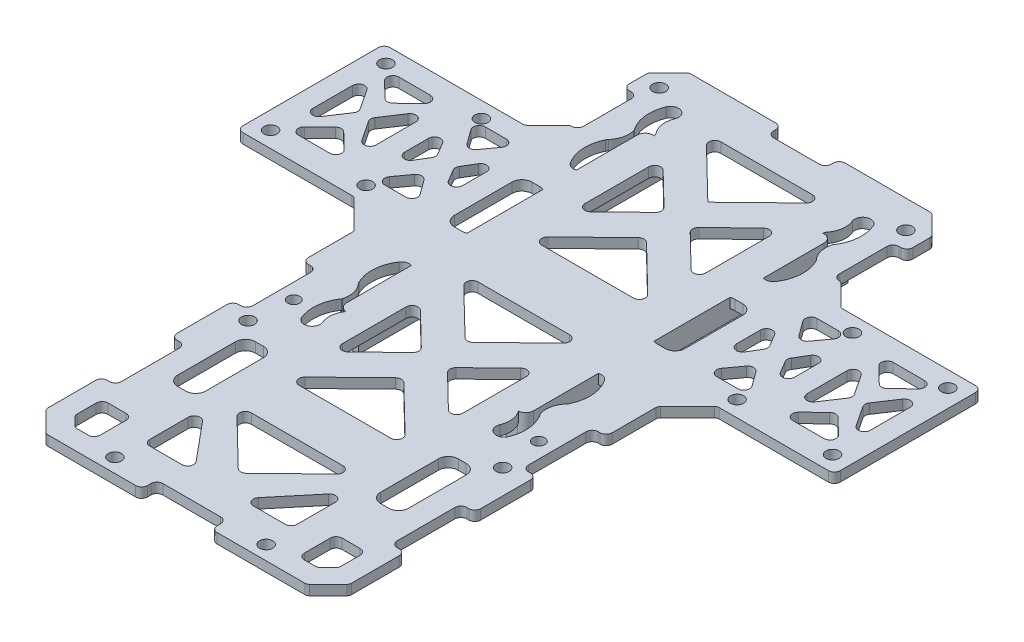
SolidWorks part; units mm, degrees
ref_plane "Ön Düzlem" through (0, 0, 0) normal (0, 0, 1) x (1, 0, 0)
ref_plane "Üst Düzlem" through (0, 0, 0) normal (0, 1, 0) x (1, 0, 0)
ref_plane "Sağ Düzlem" through (0, 0, 0) normal (1, 0, 0) x (0, 0, -1)
sketch "Çizim1" plane through (0, 0, 0) normal (0, 1, 0) x (1, 0, 0)
  line L0 (0, 0) -> (0, 152) construction
  line L1 (-5.75, 152) -> (5.75, 152)
  line L2 (7.25, 153.5) -> (7.25, 154)
  line L3 (8.75, 155.5) -> (30.05, 155.5)
  line L4 (30.8773, 155.1573) -> (35.2967, 150.7379)
  line L5 (35.6394, 149.9106) -> (35.6394, 145.6106)
  line L6 (34.1394, 144.1106) -> (33.6394, 144.1106)
  line L7 (32.1394, 142.6106) -> (32.1394, 130.6106)
  line L8 (34.4172, 128.7884) -> (39.4377, 123.7679)
  line L9 (40.2155, 123.4458) -> (73.5655, 123.4458)
  line L10 (75.0655, 121.9458) -> (75.0655, 87.9458)
  line L11 (73.5655, 86.4458) -> (46.1155, 86.4458)
  line L12 (45.2882, 86.1031) -> (38.5, 79.3148)
  line L13 (38.1573, 78.4875) -> (38.1573, 67.4875)
  line L14 (36.6573, 65.9875) -> (36.1573, 65.9875)
  line L15 (34.6573, 64.4875) -> (34.6573, 49.9875)
  line L16 (36.1573, 48.4875) -> (36.6573, 48.4875)
  line L17 (38.1573, 46.9875) -> (38.1573, 34.4875)
  line L18 (36.6573, 32.9875) -> (36.1573, 32.9875)
  line L19 (34.6573, 31.4875) -> (34.6573, 16.9875)
  line L20 (36.1573, 15.4875) -> (36.6573, 15.4875)
  line L21 (38.1573, 13.9875) -> (38.1573, 1.9875)
  line L22 (37.8351, 1.2097) -> (33.0975, -3.5279)
  line L23 (32.3197, -3.8501) -> (10.25, -3.8501)
  line L24 (8.75, -2.3501) -> (8.75, -1.5)
  line L25 (7.25, 0) -> (-7.25, 0)
  line L26 (-11.5, 144.5) -> (11.5, 144.5)
  line L27 (12.5458, 141.9246) -> (0, 129.7241)
  line L29 (4.3673, 123.0754) -> (12.5937, 131.0754)
  line L30 (15.1394, 130) -> (15.1394, 114)
  line L31 (12.5937, 112.9246) -> (4.3673, 120.9246)
  line L32 (-18.2259, 122) -> (18.2259, 122) construction
  line L33 (-11.5, 99.5) -> (11.5, 99.5)
  line L34 (12.5458, 102.0754) -> (1.0458, 113.2589)
  line L36 (-11.5, 91.5) -> (11.5, 91.5) construction
  line L37 (-11.5, 38.5) -> (11.5, 38.5)
  line L38 (12.5458, 41.0754) -> (1.0458, 52.2589)
  line L40 (15.1394, 53) -> (15.1394, 69)
  line L41 (4.3673, 59.9246) -> (12.5937, 51.9246)
  line L42 (12.5937, 70.0754) -> (4.3673, 62.0754)
  line L44 (12.5458, 80.9246) -> (1.0458, 69.7411)
  line L45 (-11.5, 83.5) -> (11.5, 83.5)
  line L46 (-12.9097, 32.5) -> (12.9097, 32.5) construction
  line L48 (12.5458, 23.9246) -> (1.0458, 12.7411)
  line L49 (-11.5, 26.5) -> (11.5, 26.5)
  line L50 (7.8474, 8.96) -> (15.8474, 18.5647)
  line L51 (18.5, 17.6047) -> (18.5, 8)
  line L52 (17, 6.5) -> (9, 6.5)
  line L53 (27.1573, 10.6499) -> (31.6573, 10.6499)
  line L54 (33.1573, 9.1499) -> (33.1573, 4.4177)
  line L55 (32.7179, 3.357) -> (30.9502, 1.5893)
  line L56 (29.8895, 1.1499) -> (27.1573, 1.1499)
  line L57 (25.6573, 2.6499) -> (25.6573, 9.1499)
  line L58 (22, 67.5) -> (26.5, 67.5) construction
  line L59 (24.5, 112) -> (26.5, 112)
  line L60 (22, 109.5) -> (22, 95)
  line L61 (24.5, 92.5) -> (26.5, 92.5)
  line L62 (29, 109.5) -> (29, 95)
  line L63 (24.5, 42.5) -> (26.5, 42.5)
  line L64 (29, 25.5) -> (29, 40)
  line L65 (24.5, 23) -> (26.5, 23)
  line L66 (22, 25.5) -> (22, 40)
  line L67 (19.1523, 99.4458) -> (36.6573, 99.4458) construction
  line L68 (37.8532, 115.7624) -> (40.5032, 112.1255)
  line L69 (42.9278, 112.1255) -> (45.5778, 115.7624)
  line L70 (44.3655, 118.1458) -> (39.0655, 118.1458)
  line L71 (40.9015, 105.5088) -> (43.9435, 105.5088) construction
  line L72 (42.9278, 98.8921) -> (45.5778, 95.2552)
  line L73 (37.8532, 95.2552) -> (40.5032, 98.8921)
  line L74 (44.3655, 92.8718) -> (39.0655, 92.8718)
  line L75 (44.4115, 104.7362) -> (46.2143, 101.7362)
  line L76 (49, 102.5088) -> (49, 108.5088)
  line L77 (46.2143, 109.2814) -> (44.4115, 106.2814)
  line L78 (41.7155, 112.5406) -> (41.7155, 108.4846) construction
  line L79 (34.431, 102.5088) -> (34.431, 108.5088)
  line L80 (39.0195, 104.7362) -> (37.2167, 101.7362)
  line L81 (37.2167, 109.2814) -> (39.0195, 106.2814)
  line L82 (58.1655, 118.1458) -> (66.0655, 118.1458)
  line L83 (67.1093, 115.5685) -> (63.1593, 111.7413)
  line L84 (61.0717, 111.7413) -> (57.1217, 115.5685)
  line L85 (67.1093, 95.4491) -> (63.1593, 99.2763)
  line L86 (58.1655, 92.8718) -> (66.0655, 92.8718)
  line L87 (61.0717, 99.2763) -> (57.1217, 95.4491)
  line L88 (63.9989, 104.6796) -> (67.3155, 99.6796)
  line L89 (70.0655, 100.5088) -> (70.0655, 110.5088)
  line L90 (67.3155, 111.338) -> (63.9989, 106.338)
  line L91 (62.1155, 113.6588) -> (62.1155, 107.6588) construction
  line L95 (54.1655, 100.5088) -> (54.1655, 110.5088)
  line L96 (60.2321, 104.6796) -> (56.9155, 99.6796)
  line L97 (56.9155, 111.338) -> (60.2321, 106.338)
  line L98 (-25.6573, 2.6499) -> (-25.6573, 9.1499)
  line L99 (-29.8895, 1.1499) -> (-27.1573, 1.1499)
  line L100 (-32.7179, 3.357) -> (-30.9502, 1.5893)
  line L101 (-33.1573, 9.1499) -> (-33.1573, 4.4177)
  line L102 (-27.1573, 10.6499) -> (-31.6573, 10.6499)
  line L103 (-17, 6.5) -> (-9, 6.5)
  line L104 (-18.5, 17.6047) -> (-18.5, 8)
  line L105 (-7.8474, 8.96) -> (-15.8474, 18.5647)
  line L106 (-12.5458, 23.9246) -> (-1.0458, 12.7411)
  line L107 (-8.75, -2.3501) -> (-8.75, -1.5)
  line L108 (-32.3197, -3.8501) -> (-10.25, -3.8501)
  line L109 (-37.8351, 1.2097) -> (-33.0975, -3.5279)
  line L110 (-38.1573, 13.9875) -> (-38.1573, 1.9875)
  line L111 (-62.1155, 113.6588) -> (-62.1155, 107.6588) construction
  line L112 (-41.7155, 112.5406) -> (-41.7155, 108.4846) construction
  line L113 (-40.9015, 105.5088) -> (-43.9435, 105.5088) construction
  line L114 (-19.1523, 99.4458) -> (-36.6573, 99.4458) construction
  line L115 (-22, 67.5) -> (-26.5, 67.5) construction
  line L116 (-56.9155, 111.338) -> (-60.2321, 106.338)
  line L117 (-60.2321, 104.6796) -> (-56.9155, 99.6796)
  line L118 (-54.1655, 100.5088) -> (-54.1655, 110.5088)
  line L119 (-67.3155, 111.338) -> (-63.9989, 106.338)
  line L120 (-70.0655, 100.5088) -> (-70.0655, 110.5088)
  line L121 (-63.9989, 104.6796) -> (-67.3155, 99.6796)
  line L122 (-61.0717, 99.2763) -> (-57.1217, 95.4491)
  line L123 (-58.1655, 92.8718) -> (-66.0655, 92.8718)
  line L124 (-67.1093, 95.4491) -> (-63.1593, 99.2763)
  line L125 (-61.0717, 111.7413) -> (-57.1217, 115.5685)
  line L126 (-67.1093, 115.5685) -> (-63.1593, 111.7413)
  line L127 (-58.1655, 118.1458) -> (-66.0655, 118.1458)
  line L128 (-37.2167, 109.2814) -> (-39.0195, 106.2814)
  line L129 (-39.0195, 104.7362) -> (-37.2167, 101.7362)
  line L130 (-34.431, 102.5088) -> (-34.431, 108.5088)
  line L131 (-46.2143, 109.2814) -> (-44.4115, 106.2814)
  line L132 (-49, 102.5088) -> (-49, 108.5088)
  line L133 (-44.4115, 104.7362) -> (-46.2143, 101.7362)
  line L134 (-44.3655, 92.8718) -> (-39.0655, 92.8718)
  line L135 (-37.8532, 95.2552) -> (-40.5032, 98.8921)
  line L136 (-42.9278, 98.8921) -> (-45.5778, 95.2552)
  line L137 (-44.3655, 118.1458) -> (-39.0655, 118.1458)
  line L138 (-42.9278, 112.1255) -> (-45.5778, 115.7624)
  line L139 (-37.8532, 115.7624) -> (-40.5032, 112.1255)
  line L140 (-22, 25.5) -> (-22, 40)
  line L141 (-24.5, 23) -> (-26.5, 23)
  line L142 (-29, 25.5) -> (-29, 40)
  line L143 (-24.5, 42.5) -> (-26.5, 42.5)
  line L144 (-29, 109.5) -> (-29, 95)
  line L145 (-24.5, 92.5) -> (-26.5, 92.5)
  line L146 (-22, 109.5) -> (-22, 95)
  line L147 (-24.5, 112) -> (-26.5, 112)
  line L148 (-12.5458, 80.9246) -> (-1.0458, 69.7411)
  line L149 (-12.5937, 70.0754) -> (-4.3673, 62.0754)
  line L150 (-4.3673, 59.9246) -> (-12.5937, 51.9246)
  line L151 (-15.1394, 53) -> (-15.1394, 69)
  line L152 (-12.5458, 41.0754) -> (-1.0458, 52.2589)
  line L153 (-12.5458, 102.0754) -> (-1.0458, 113.2589)
  line L154 (-12.5937, 112.9246) -> (-4.3673, 120.9246)
  line L155 (-15.1394, 130) -> (-15.1394, 114)
  line L156 (-4.3673, 123.0754) -> (-12.5937, 131.0754)
  line L157 (-12.5458, 141.9246) -> (0, 129.7241)
  line L158 (-36.1573, 15.4875) -> (-36.6573, 15.4875)
  line L159 (-34.6573, 31.4875) -> (-34.6573, 16.9875)
  line L160 (-36.6573, 32.9875) -> (-36.1573, 32.9875)
  line L161 (-38.1573, 46.9875) -> (-38.1573, 34.4875)
  line L162 (-36.1573, 48.4875) -> (-36.6573, 48.4875)
  line L163 (-34.6573, 64.4875) -> (-34.6573, 49.9875)
  line L164 (-36.6573, 65.9875) -> (-36.1573, 65.9875)
  line L165 (-38.1573, 78.4875) -> (-38.1573, 67.4875)
  line L166 (-45.2882, 86.1031) -> (-38.5, 79.3148)
  line L167 (-73.5655, 86.4458) -> (-46.1155, 86.4458)
  line L168 (-75.0655, 121.9458) -> (-75.0655, 87.9458)
  line L169 (-40.2155, 123.4458) -> (-73.5655, 123.4458)
  line L170 (-34.4172, 128.7884) -> (-39.4377, 123.7679)
  line L171 (-32.1394, 142.6106) -> (-32.1394, 130.6106)
  line L172 (-34.1394, 144.1106) -> (-33.6394, 144.1106)
  line L173 (-35.6394, 149.9106) -> (-35.6394, 145.6106)
  line L174 (-30.8773, 155.1573) -> (-35.2967, 150.7379)
  line L175 (-8.75, 155.5) -> (-30.05, 155.5)
  line L176 (-7.25, 153.5) -> (-7.25, 154)
  arc A0 (5.75, 152) -> (7.25, 153.5) centre (5.75, 153.5) ccw
  arc A1 (7.25, 154) -> (8.75, 155.5) centre (8.75, 154) cw
  arc A2 (30.05, 155.5) -> (30.8773, 155.1573) centre (30.05, 154.33) cw
  arc A3 (35.2967, 150.7379) -> (35.6394, 149.9106) centre (34.4694, 149.9106) cw
  arc A4 (35.6394, 145.6106) -> (34.1394, 144.1106) centre (34.1394, 145.6106) cw
  arc A5 (33.6394, 144.1106) -> (32.1394, 142.6106) centre (33.6394, 142.6106) ccw
  arc A6 (32.1394, 130.6106) -> (33.6394, 129.1106) centre (33.6394, 130.6106) ccw
  arc A7 (34.4172, 128.7884) -> (33.6394, 129.1106) centre (33.6394, 128.0106) ccw
  arc A8 (39.4377, 123.7679) -> (40.2155, 123.4458) centre (40.2155, 124.5458) ccw
  arc A9 (73.5655, 123.4458) -> (75.0655, 121.9458) centre (73.5655, 121.9458) cw
  arc A10 (75.0655, 87.9458) -> (73.5655, 86.4458) centre (73.5655, 87.9458) cw
  arc A11 (46.1155, 86.4458) -> (45.2882, 86.1031) centre (46.1155, 85.2758) ccw
  arc A12 (38.5, 79.3148) -> (38.1573, 78.4875) centre (39.3273, 78.4875) ccw
  arc A13 (36.1573, 65.9875) -> (34.6573, 64.4875) centre (36.1573, 64.4875) ccw
  arc A14 (38.1573, 67.4875) -> (36.6573, 65.9875) centre (36.6573, 67.4875) cw
  arc A15 (36.6573, 48.4875) -> (38.1573, 46.9875) centre (36.6573, 46.9875) cw
  arc A16 (34.6573, 49.9875) -> (36.1573, 48.4875) centre (36.1573, 49.9875) ccw
  arc A17 (36.1573, 32.9875) -> (34.6573, 31.4875) centre (36.1573, 31.4875) ccw
  arc A18 (38.1573, 34.4875) -> (36.6573, 32.9875) centre (36.6573, 34.4875) cw
  arc A19 (36.6573, 15.4875) -> (38.1573, 13.9875) centre (36.6573, 13.9875) cw
  arc A20 (34.6573, 16.9875) -> (36.1573, 15.4875) centre (36.1573, 16.9875) ccw
  arc A21 (38.1573, 1.9875) -> (37.8351, 1.2097) centre (37.0573, 1.9875) cw
  arc A22 (33.0975, -3.5279) -> (32.3197, -3.8501) centre (32.3197, -2.7501) cw
  arc A23 (8.75, -1.5) -> (7.25, 0) centre (7.25, -1.5) ccw
  arc A24 (10.25, -3.8501) -> (8.75, -2.3501) centre (10.25, -2.3501) cw
  arc A25 (11.5, 144.5) -> (12.5458, 141.9246) centre (11.5, 143) cw
  arc A27 (12.5937, 131.0754) -> (15.1394, 130) centre (13.6394, 130) cw
  arc A28 (15.1394, 114) -> (12.5937, 112.9246) centre (13.6394, 114) cw
  arc A29 (4.3673, 123.0754) -> (4.3673, 120.9246) centre (5.4131, 122) ccw
  arc A30 (11.5, 99.5) -> (12.5458, 102.0754) centre (11.5, 101) ccw
  arc A32 (11.5, 38.5) -> (12.5458, 41.0754) centre (11.5, 40) ccw
  arc A34 (12.5937, 51.9246) -> (15.1394, 53) centre (13.6394, 53) ccw
  arc A35 (15.1394, 69) -> (12.5937, 70.0754) centre (13.6394, 69) ccw
  arc A36 (4.3673, 59.9246) -> (4.3673, 62.0754) centre (5.4131, 61) cw
  arc A38 (11.5, 83.5) -> (12.5458, 80.9246) centre (11.5, 82) cw
  arc A40 (11.5, 26.5) -> (12.5458, 23.9246) centre (11.5, 25) cw
  arc A41 (15.8474, 18.5647) -> (18.5, 17.6047) centre (17, 17.6047) cw
  arc A42 (18.5, 8) -> (17, 6.5) centre (17, 8) cw
  arc A43 (7.8474, 8.96) -> (9, 6.5) centre (9, 8) ccw
  arc A44 (31.6573, 10.6499) -> (33.1573, 9.1499) centre (31.6573, 9.1499) cw
  arc A45 (27.1573, 10.6499) -> (25.6573, 9.1499) centre (27.1573, 9.1499) ccw
  arc A46 (33.1573, 4.4177) -> (32.7179, 3.357) centre (31.6573, 4.4177) cw
  arc A47 (30.9502, 1.5893) -> (29.8895, 1.1499) centre (29.8895, 2.6499) cw
  arc A48 (27.1573, 1.1499) -> (25.6573, 2.6499) centre (27.1573, 2.6499) cw
  arc A49 (22, 95) -> (24.5, 92.5) centre (24.5, 95) ccw
  arc A50 (26.5, 92.5) -> (29, 95) centre (26.5, 95) ccw
  arc A51 (26.5, 112) -> (29, 109.5) centre (26.5, 109.5) cw
  arc A52 (24.5, 112) -> (22, 109.5) centre (24.5, 109.5) ccw
  arc A53 (26.5, 42.5) -> (29, 40) centre (26.5, 40) cw
  arc A54 (26.5, 23) -> (29, 25.5) centre (26.5, 25.5) ccw
  arc A55 (22, 40) -> (24.5, 42.5) centre (24.5, 40) cw
  arc A56 (24.5, 23) -> (22, 25.5) centre (24.5, 25.5) cw
  arc A57 (23.1394, 137.067) -> (24.1394, 144.5) centre (17.2022, 141.6495) ccw construction
  arc A62 (24.7227, 135.845) -> (25.9893, 145.2601) centre (17.2022, 141.6495) ccw
  arc A63 (21.5562, 138.289) -> (22.2895, 143.7399) centre (17.2022, 141.6495) ccw
  arc A64 (21.5562, 138.289) -> (24.7227, 135.845) centre (23.1394, 137.067) ccw
  arc A65 (25.9893, 145.2601) -> (22.2895, 143.7399) centre (24.1394, 144.5) ccw
  arc A66 (24.6394, 129.567) -> (23.1394, 137.067) centre (30.2159, 134.5823) cw construction
  arc A71 (21.2524, 137.7296) -> (23.1524, 128.2296) centre (30.2159, 134.5823) ccw
  arc A72 (25.0265, 136.4044) -> (26.1265, 130.9044) centre (30.2159, 134.5823) ccw
  arc A73 (25.0265, 136.4044) -> (21.2524, 137.7296) centre (23.1394, 137.067) ccw
  arc A74 (23.1524, 128.2296) -> (26.1265, 130.9044) centre (24.6394, 129.567) ccw
  arc A75 (24.1394, 122.0837) -> (24.6394, 129.567) centre (17.9087, 126.2583) ccw construction
  arc A76 (25.8009, 120.9704) -> (26.4343, 130.4493) centre (17.9087, 126.2583) ccw
  arc A77 (22.4779, 123.1969) -> (22.8446, 128.6847) centre (17.9087, 126.2583) ccw
  arc A78 (22.4779, 123.1969) -> (25.8009, 120.9704) centre (24.1394, 122.0837) ccw
  arc A79 (26.4343, 130.4493) -> (22.8446, 128.6847) centre (24.6394, 129.567) ccw
  arc A80 (24.6394, 69.3246) -> (23.1394, 61.8246) centre (30.2159, 64.3093) ccw construction
  arc A81 (21.2524, 61.162) -> (23.1524, 70.662) centre (30.2159, 64.3093) cw
  arc A82 (25.0265, 62.4871) -> (26.1265, 67.9871) centre (30.2159, 64.3093) cw
  arc A83 (25.0265, 62.4871) -> (21.2524, 61.162) centre (23.1394, 61.8246) cw
  arc A84 (23.1524, 70.662) -> (26.1265, 67.9871) centre (24.6394, 69.3246) cw
  arc A85 (23.1394, 61.8246) -> (24.1394, 54.3915) centre (17.2022, 57.242) cw construction
  arc A86 (24.7227, 63.0466) -> (25.9893, 53.6314) centre (17.2022, 57.242) cw
  arc A87 (21.5562, 60.6025) -> (22.2895, 55.1516) centre (17.2022, 57.242) cw
  arc A88 (21.5562, 60.6025) -> (24.7227, 63.0466) centre (23.1394, 61.8246) cw
  arc A89 (25.9893, 53.6314) -> (22.2895, 55.1516) centre (24.1394, 54.3915) cw
  arc A90 (24.1394, 76.8079) -> (24.6394, 69.3246) centre (17.9087, 72.6332) cw construction
  arc A91 (25.8009, 77.9211) -> (26.4343, 68.4422) centre (17.9087, 72.6332) cw
  arc A92 (22.4779, 75.6946) -> (22.8446, 70.2069) centre (17.9087, 72.6332) cw
  arc A93 (22.4779, 75.6946) -> (25.8009, 77.9211) centre (24.1394, 76.8079) cw
  arc A94 (26.4343, 68.4422) -> (22.8446, 70.2069) centre (24.6394, 69.3246) cw
  arc A95 (40.5032, 112.1255) -> (42.9278, 112.1255) centre (41.7155, 113.0088) ccw
  arc A96 (45.5778, 115.7624) -> (44.3655, 118.1458) centre (44.3655, 116.6458) ccw
  arc A97 (37.8532, 115.7624) -> (39.0655, 118.1458) centre (39.0655, 116.6458) cw
  arc A98 (40.5032, 98.8921) -> (42.9278, 98.8921) centre (41.7155, 98.0088) cw
  arc A99 (45.5778, 95.2552) -> (44.3655, 92.8718) centre (44.3655, 94.3718) cw
  arc A100 (37.8532, 95.2552) -> (39.0655, 92.8718) centre (39.0655, 94.3718) ccw
  arc A101 (49, 108.5088) -> (46.2143, 109.2814) centre (47.5, 108.5088) ccw
  arc A102 (46.2143, 101.7362) -> (49, 102.5088) centre (47.5, 102.5088) ccw
  arc A103 (44.4115, 104.7362) -> (44.4115, 106.2814) centre (45.6972, 105.5088) cw
  arc A104 (37.2167, 101.7362) -> (34.431, 102.5088) centre (35.931, 102.5088) cw
  arc A105 (34.431, 108.5088) -> (37.2167, 109.2814) centre (35.931, 108.5088) cw
  arc A106 (39.0195, 104.7362) -> (39.0195, 106.2814) centre (37.7338, 105.5088) ccw
  arc A107 (66.0655, 118.1458) -> (67.1093, 115.5685) centre (66.0655, 116.6458) cw
  arc A108 (63.1593, 111.7413) -> (61.0717, 111.7413) centre (62.1155, 112.8186) cw
  arc A109 (58.1655, 118.1458) -> (57.1217, 115.5685) centre (58.1655, 116.6458) ccw
  arc A110 (66.0655, 92.8718) -> (67.1093, 95.4491) centre (66.0655, 94.3718) ccw
  arc A111 (63.1593, 99.2763) -> (61.0717, 99.2763) centre (62.1155, 98.199) ccw
  arc A112 (58.1655, 92.8718) -> (57.1217, 95.4491) centre (58.1655, 94.3718) cw
  arc A113 (67.3155, 99.6796) -> (70.0655, 100.5088) centre (68.5655, 100.5088) ccw
  arc A114 (63.9989, 104.6796) -> (63.9989, 106.338) centre (65.2489, 105.5088) cw
  arc A115 (70.0655, 110.5088) -> (67.3155, 111.338) centre (68.5655, 110.5088) ccw
  arc A119 (56.9155, 99.6796) -> (54.1655, 100.5088) centre (55.6655, 100.5088) cw
  arc A120 (60.2321, 104.6796) -> (60.2321, 106.338) centre (58.9821, 105.5088) ccw
  arc A121 (54.1655, 110.5088) -> (56.9155, 111.338) centre (55.6655, 110.5088) cw
  arc A122 (-27.1573, 1.1499) -> (-25.6573, 2.6499) centre (-27.1573, 2.6499) ccw
  arc A123 (-30.9502, 1.5893) -> (-29.8895, 1.1499) centre (-29.8895, 2.6499) ccw
  arc A124 (-33.1573, 4.4177) -> (-32.7179, 3.357) centre (-31.6573, 4.4177) ccw
  arc A125 (-27.1573, 10.6499) -> (-25.6573, 9.1499) centre (-27.1573, 9.1499) cw
  arc A126 (-31.6573, 10.6499) -> (-33.1573, 9.1499) centre (-31.6573, 9.1499) ccw
  arc A127 (-7.8474, 8.96) -> (-9, 6.5) centre (-9, 8) cw
  arc A128 (-18.5, 8) -> (-17, 6.5) centre (-17, 8) ccw
  arc A129 (-15.8474, 18.5647) -> (-18.5, 17.6047) centre (-17, 17.6047) ccw
  arc A130 (-10.25, -3.8501) -> (-8.75, -2.3501) centre (-10.25, -2.3501) ccw
  arc A131 (-8.75, -1.5) -> (-7.25, 0) centre (-7.25, -1.5) cw
  arc A132 (-33.0975, -3.5279) -> (-32.3197, -3.8501) centre (-32.3197, -2.7501) ccw
  arc A133 (-38.1573, 1.9875) -> (-37.8351, 1.2097) centre (-37.0573, 1.9875) ccw
  arc A134 (-36.6573, 15.4875) -> (-38.1573, 13.9875) centre (-36.6573, 13.9875) ccw
  arc A135 (-54.1655, 110.5088) -> (-56.9155, 111.338) centre (-55.6655, 110.5088) ccw
  arc A136 (-60.2321, 104.6796) -> (-60.2321, 106.338) centre (-58.9821, 105.5088) cw
  arc A137 (-56.9155, 99.6796) -> (-54.1655, 100.5088) centre (-55.6655, 100.5088) ccw
  arc A138 (-70.0655, 110.5088) -> (-67.3155, 111.338) centre (-68.5655, 110.5088) cw
  arc A139 (-63.9989, 104.6796) -> (-63.9989, 106.338) centre (-65.2489, 105.5088) ccw
  arc A140 (-67.3155, 99.6796) -> (-70.0655, 100.5088) centre (-68.5655, 100.5088) cw
  arc A141 (-58.1655, 92.8718) -> (-57.1217, 95.4491) centre (-58.1655, 94.3718) ccw
  arc A142 (-63.1593, 99.2763) -> (-61.0717, 99.2763) centre (-62.1155, 98.199) cw
  arc A143 (-66.0655, 92.8718) -> (-67.1093, 95.4491) centre (-66.0655, 94.3718) cw
  arc A144 (-58.1655, 118.1458) -> (-57.1217, 115.5685) centre (-58.1655, 116.6458) cw
  arc A145 (-63.1593, 111.7413) -> (-61.0717, 111.7413) centre (-62.1155, 112.8186) ccw
  arc A146 (-66.0655, 118.1458) -> (-67.1093, 115.5685) centre (-66.0655, 116.6458) ccw
  arc A147 (-39.0195, 104.7362) -> (-39.0195, 106.2814) centre (-37.7338, 105.5088) cw
  arc A148 (-34.431, 108.5088) -> (-37.2167, 109.2814) centre (-35.931, 108.5088) ccw
  arc A149 (-37.2167, 101.7362) -> (-34.431, 102.5088) centre (-35.931, 102.5088) ccw
  arc A150 (-44.4115, 104.7362) -> (-44.4115, 106.2814) centre (-45.6972, 105.5088) ccw
  arc A151 (-46.2143, 101.7362) -> (-49, 102.5088) centre (-47.5, 102.5088) cw
  arc A152 (-49, 108.5088) -> (-46.2143, 109.2814) centre (-47.5, 108.5088) cw
  arc A153 (-37.8532, 95.2552) -> (-39.0655, 92.8718) centre (-39.0655, 94.3718) cw
  arc A154 (-45.5778, 95.2552) -> (-44.3655, 92.8718) centre (-44.3655, 94.3718) ccw
  arc A155 (-40.5032, 98.8921) -> (-42.9278, 98.8921) centre (-41.7155, 98.0088) ccw
  arc A156 (-37.8532, 115.7624) -> (-39.0655, 118.1458) centre (-39.0655, 116.6458) ccw
  arc A157 (-45.5778, 115.7624) -> (-44.3655, 118.1458) centre (-44.3655, 116.6458) cw
  arc A158 (-40.5032, 112.1255) -> (-42.9278, 112.1255) centre (-41.7155, 113.0088) cw
  arc A159 (-24.5, 23) -> (-22, 25.5) centre (-24.5, 25.5) ccw
  arc A160 (-22, 40) -> (-24.5, 42.5) centre (-24.5, 40) ccw
  arc A161 (-26.5, 23) -> (-29, 25.5) centre (-26.5, 25.5) cw
  arc A162 (-26.5, 42.5) -> (-29, 40) centre (-26.5, 40) ccw
  arc A163 (-24.5, 112) -> (-22, 109.5) centre (-24.5, 109.5) cw
  arc A164 (-26.5, 112) -> (-29, 109.5) centre (-26.5, 109.5) ccw
  arc A165 (-26.5, 92.5) -> (-29, 95) centre (-26.5, 95) cw
  arc A166 (-22, 95) -> (-24.5, 92.5) centre (-24.5, 95) cw
  arc A167 (-11.5, 26.5) -> (-12.5458, 23.9246) centre (-11.5, 25) ccw
  arc A168 (-11.5, 83.5) -> (-12.5458, 80.9246) centre (-11.5, 82) ccw
  arc A169 (-4.3673, 59.9246) -> (-4.3673, 62.0754) centre (-5.4131, 61) ccw
  arc A170 (-15.1394, 69) -> (-12.5937, 70.0754) centre (-13.6394, 69) cw
  arc A171 (-12.5937, 51.9246) -> (-15.1394, 53) centre (-13.6394, 53) cw
  arc A172 (-11.5, 38.5) -> (-12.5458, 41.0754) centre (-11.5, 40) cw
  arc A173 (-11.5, 99.5) -> (-12.5458, 102.0754) centre (-11.5, 101) cw
  arc A174 (-4.3673, 123.0754) -> (-4.3673, 120.9246) centre (-5.4131, 122) cw
  arc A175 (-15.1394, 114) -> (-12.5937, 112.9246) centre (-13.6394, 114) ccw
  arc A176 (-12.5937, 131.0754) -> (-15.1394, 130) centre (-13.6394, 130) ccw
  arc A177 (-11.5, 144.5) -> (-12.5458, 141.9246) centre (-11.5, 143) ccw
  arc A178 (-34.6573, 16.9875) -> (-36.1573, 15.4875) centre (-36.1573, 16.9875) cw
  arc A179 (-38.1573, 34.4875) -> (-36.6573, 32.9875) centre (-36.6573, 34.4875) ccw
  arc A180 (-36.1573, 32.9875) -> (-34.6573, 31.4875) centre (-36.1573, 31.4875) cw
  arc A181 (-34.6573, 49.9875) -> (-36.1573, 48.4875) centre (-36.1573, 49.9875) cw
  arc A182 (-36.6573, 48.4875) -> (-38.1573, 46.9875) centre (-36.6573, 46.9875) ccw
  arc A183 (-38.1573, 67.4875) -> (-36.6573, 65.9875) centre (-36.6573, 67.4875) ccw
  arc A184 (-36.1573, 65.9875) -> (-34.6573, 64.4875) centre (-36.1573, 64.4875) cw
  arc A185 (-38.5, 79.3148) -> (-38.1573, 78.4875) centre (-39.3273, 78.4875) cw
  arc A186 (-46.1155, 86.4458) -> (-45.2882, 86.1031) centre (-46.1155, 85.2758) cw
  arc A187 (-75.0655, 87.9458) -> (-73.5655, 86.4458) centre (-73.5655, 87.9458) ccw
  arc A188 (-73.5655, 123.4458) -> (-75.0655, 121.9458) centre (-73.5655, 121.9458) ccw
  arc A189 (-39.4377, 123.7679) -> (-40.2155, 123.4458) centre (-40.2155, 124.5458) cw
  arc A190 (-34.4172, 128.7884) -> (-33.6394, 129.1106) centre (-33.6394, 128.0106) cw
  arc A191 (-32.1394, 130.6106) -> (-33.6394, 129.1106) centre (-33.6394, 130.6106) cw
  arc A192 (-33.6394, 144.1106) -> (-32.1394, 142.6106) centre (-33.6394, 142.6106) cw
  arc A193 (-35.6394, 145.6106) -> (-34.1394, 144.1106) centre (-34.1394, 145.6106) ccw
  arc A194 (-35.2967, 150.7379) -> (-35.6394, 149.9106) centre (-34.4694, 149.9106) ccw
  arc A195 (-30.05, 155.5) -> (-30.8773, 155.1573) centre (-30.05, 154.33) ccw
  arc A196 (-7.25, 154) -> (-8.75, 155.5) centre (-8.75, 154) ccw
  arc A197 (-5.75, 152) -> (-7.25, 153.5) centre (-5.75, 153.5) cw
  arc A198 (-24.1394, 76.8079) -> (-24.6394, 69.3246) centre (-17.9087, 72.6332) ccw construction
  arc A199 (-25.8009, 77.9211) -> (-26.4343, 68.4422) centre (-17.9087, 72.6332) ccw
  arc A200 (-22.4779, 75.6946) -> (-22.8446, 70.2069) centre (-17.9087, 72.6332) ccw
  arc A201 (-22.4779, 75.6946) -> (-25.8009, 77.9211) centre (-24.1394, 76.8079) ccw
  arc A202 (-26.4343, 68.4422) -> (-22.8446, 70.2069) centre (-24.6394, 69.3246) ccw
  arc A203 (-23.1394, 61.8246) -> (-24.1394, 54.3915) centre (-17.2022, 57.242) ccw construction
  arc A204 (-24.7227, 63.0466) -> (-25.9893, 53.6314) centre (-17.2022, 57.242) ccw
  arc A205 (-21.5562, 60.6025) -> (-22.2895, 55.1516) centre (-17.2022, 57.242) ccw
  arc A206 (-21.5562, 60.6025) -> (-24.7227, 63.0466) centre (-23.1394, 61.8246) ccw
  arc A207 (-25.9893, 53.6314) -> (-22.2895, 55.1516) centre (-24.1394, 54.3915) ccw
  arc A208 (-24.6394, 69.3246) -> (-23.1394, 61.8246) centre (-30.2159, 64.3093) cw construction
  arc A209 (-21.2524, 61.162) -> (-23.1524, 70.662) centre (-30.2159, 64.3093) ccw
  arc A210 (-25.0265, 62.4871) -> (-26.1265, 67.9871) centre (-30.2159, 64.3093) ccw
  arc A211 (-25.0265, 62.4871) -> (-21.2524, 61.162) centre (-23.1394, 61.8246) ccw
  arc A212 (-23.1524, 70.662) -> (-26.1265, 67.9871) centre (-24.6394, 69.3246) ccw
  arc A213 (-24.1394, 122.0837) -> (-24.6394, 129.567) centre (-17.9087, 126.2583) cw construction
  arc A214 (-25.8009, 120.9704) -> (-26.4343, 130.4493) centre (-17.9087, 126.2583) cw
  arc A215 (-22.4779, 123.1969) -> (-22.8446, 128.6847) centre (-17.9087, 126.2583) cw
  arc A216 (-22.4779, 123.1969) -> (-25.8009, 120.9704) centre (-24.1394, 122.0837) cw
  arc A217 (-26.4343, 130.4493) -> (-22.8446, 128.6847) centre (-24.6394, 129.567) cw
  arc A218 (-24.6394, 129.567) -> (-23.1394, 137.067) centre (-30.2159, 134.5823) ccw construction
  arc A219 (-21.2524, 137.7296) -> (-23.1524, 128.2296) centre (-30.2159, 134.5823) cw
  arc A220 (-25.0265, 136.4044) -> (-26.1265, 130.9044) centre (-30.2159, 134.5823) cw
  arc A221 (-25.0265, 136.4044) -> (-21.2524, 137.7296) centre (-23.1394, 137.067) cw
  arc A222 (-23.1524, 128.2296) -> (-26.1265, 130.9044) centre (-24.6394, 129.567) cw
  arc A223 (-23.1394, 137.067) -> (-24.1394, 144.5) centre (-17.2022, 141.6495) cw construction
  arc A224 (-24.7227, 135.845) -> (-25.9893, 145.2601) centre (-17.2022, 141.6495) cw
  arc A225 (-21.5562, 138.289) -> (-22.2895, 143.7399) centre (-17.2022, 141.6495) cw
  arc A226 (-21.5562, 138.289) -> (-24.7227, 135.845) centre (-23.1394, 137.067) cw
  arc A227 (-25.9893, 145.2601) -> (-22.2895, 143.7399) centre (-24.1394, 144.5) cw
  arc A228 (1.0458, 113.2589) -> (-1.0458, 113.2589) centre (0, 112.1836) ccw
  arc A229 (-1.0458, 69.7411) -> (1.0458, 69.7411) centre (0, 70.8164) ccw
  arc A230 (1.0458, 52.2589) -> (-1.0458, 52.2589) centre (0, 51.1836) ccw
  arc A231 (-1.0458, 12.7411) -> (1.0458, 12.7411) centre (0, 13.8164) ccw
  point P9 (7.25, 152)
  point P17 (35.6394, 150.3952)
  point P22 (35.6394, 144.1106)
  point P28 (32.1394, 136.1106)
  point P37 (75.0655, 123.4458)
  point P45 (45.6309, 86.4458)
  point P54 (38.1573, 65.9875)
  point P61 (34.6573, 48.4875)
  point P74 (34.6573, 20.4875)
  point P81 (34.6573, 15.4875)
  point P84 (38.1573, 1.5319)
  point P89 (10.3197, -3.8501)
  point P96 (0, 131.8865)
  point P106 (0, 144.5)
  point P117 (0, 99.5)
  point P133 (0, 38.5)
  point P142 (0, 83.5)
  point P166 (33.1573, 10.6499)
  point P169 (25.6573, 10.6499)
  point P194 (24.6353, 140.6495)
  point P202 (22.8615, 133.1114)
  point P207 (25.392, 125.7583)
  point P220 (22.8615, 65.7801)
  point P228 (24.6353, 58.242)
  point P236 (25.392, 73.1332)
  point P359 (-25.6573, 10.6499)
  point P360 (-33.1573, 10.6499)
  point P361 (-10.3197, -3.8501)
  point P362 (-38.1573, 1.5319)
  point P374 (0, 32.5)
  point P375 (0, 91.5)
  point P376 (0, 122)
  point P563 (0, 26.5)
  point P566 (-25.392, 73.1332)
  point P574 (-24.6353, 58.242)
  point P582 (-22.8615, 65.7801)
  point P590 (-25.392, 125.7583)
  point P598 (-22.8615, 133.1114)
  point P606 (-24.6353, 140.6495)
  point P611 (-34.6573, 15.4875)
  point P612 (-34.6573, 20.4875)
  point P613 (-34.6573, 48.4875)
  point P614 (-38.1573, 65.9875)
  point P615 (-45.6309, 86.4458)
  point P616 (-75.0655, 123.4458)
  point P617 (-32.1394, 136.1106)
  point P618 (-35.6394, 144.1106)
  point P619 (-35.6394, 150.3952)
  point P620 (-7.25, 152)
  point P623 (0, 114.2759)
  point P626 (0, 68.7241)
  point P629 (0, 53.2759)
  point P632 (0, 11.7241)
  dimension "D2" = 1.5
  dimension "D3" = 1.5
  dimension "D6" = 1.17
  dimension "D11" = 1.17
  dimension "D12" = 1.5
  dimension "D13" = 1.5
  dimension "D16" = 1.5
  dimension "D18" = 1.1
  dimension "D19" = 1.1
  dimension "D22" = 1.5
  dimension "D23" = 1.5
  dimension "D26" = 1.17
  dimension "D27" = 1.17
  dimension "D31" = 1.5
  dimension "D34" = 1.5
  dimension "D36" = 1.5
  dimension "D40" = 1.5
  dimension "D43" = 1.1
  dimension "D44" = 1.1
  dimension "D48" = 1.5
  dimension "D49" = 1.5
  dimension "D50" = 1.5
  dimension "D53" = 2.5
  dimension "D55" = 1.5
  dimension "D61" = 1.5
  dimension "D67" = 1.5
  dimension "D66" = 1.5
  dimension "D79" = 2
  dimension "D85" = 5.5
  dimension "D90" = 5.5
  dimension "D91" = 2
  dimension "D94" = 1.5
  dimension "D100" = 1.5
  dimension "D104" = 1.5
  dimension "D108" = 1.5
  dimension "D112" = 1.5
  dimension "D113" = 1.5
  dimension "D114" = 1.5
  dimension "D115" = 1.5
  dimension "D1" = 7.25
  dimension "D4" = 0.5
  dimension "D5" = 152
  dimension "D7" = 6.25
  dimension "D8" = 135
  dimension "D9" = 21.3
  dimension "D10" = 4.3
  dimension "D14" = 0.5
  dimension "D15" = 12
  dimension "D17" = 135
  dimension "D20" = 7.1
  dimension "D21" = 33.35
  dimension "D24" = 34
  dimension "D25" = 27.45
  dimension "D28" = 135
  dimension "D29" = 9.6
  dimension "D30" = 11
  dimension "D32" = 0.5
  dimension "D33" = 14.5
  dimension "D35" = 0.5
  dimension "D37" = 12.5
  dimension "D38" = 0.5
  dimension "D39" = 14.5
  dimension "D41" = 0.5
  dimension "D42" = 12
  dimension "D45" = 6.7
  dimension "D46" = 135
  dimension "D47" = 22
  dimension "D51" = 11.5
  dimension "D52" = 17.5
  dimension "D54" = 7.5
  dimension "D56" = 22
  dimension "D57" = 16
  dimension "D58" = 17
  dimension "D59" = 8
  dimension "D60" = 6
  dimension "D62" = 8
  dimension "D63" = 9
  dimension "D64" = 8
  dimension "D65" = 4.5
  dimension "D68" = 6.5
  dimension "D69" = 135
  dimension "D70" = 5
  dimension "D71" = 5
  dimension "D72" = 2.5
  dimension "D73" = 12.5
  dimension "D74" = 14.5
  dimension "D75" = 2
  dimension "D76" = 40
  dimension "D77" = 22
  dimension "D78" = 25
  dimension "D80" = 7.5
  dimension "D81" = 5.5
  dimension "D82" = 8
  dimension "D83" = 9
  dimension "D84" = 11
  dimension "D86" = 7.5
  dimension "D87" = 2
  dimension "D88" = 7.5
  dimension "D89" = 7.5
  dimension "D92" = 8
  dimension "D93" = 24
  dimension "D95" = 5.3
  dimension "D96" = 4.5
  dimension "D97" = 5.3
  dimension "D98" = 36
  dimension "D99" = 7.5
  dimension "D101" = 6
  dimension "D102" = 3.5
  dimension "D103" = 20
  dimension "D105" = 7.9
  dimension "D106" = 5.5
  dimension "D107" = 9
  dimension "D109" = 10
  dimension "D110" = 6
  dimension "D111" = 5
  dimension "D116" = 7.25
extrude "Yükseklik-Ekstrüzyon1" add sketch "Çizim1" along normal blind 2.5 contours L1 A197 L176 A196 L175 A195 L174 A194 L173 A193 L172 A192 L171 A191 A190 L170 A189 L169 A188 L168 A187 L167 A186 L166 A185 L165 A183 L164 A184 L163 A181 L162 A182 L161 A179 L160 A180 L159 A178 L158 A134 L110 A133 L109 A132 L108 A130 L107 A131 L25 A23
sketch "Çizim3" plane through (0, 0, 0) normal (0, -1, 0) x (1, 0, 0)
  line L0 (0, -152) -> (0, 0) construction
  line L1 (-5.75, -152) -> (5.75, -152) construction
  line L2 (-8.75, -155.5) -> (-30.05, -155.5) construction
  line L3 (-32.3197, 3.8501) -> (-10.25, 3.8501) construction
  line L4 (-75.0655, -104.9458) -> (0, -104.9458) construction
  line L5 (-75.0655, -121.9458) -> (-75.0655, -87.9458) construction
  circle A0 centre (-31, -148.5) radius 1.65
  circle A1 centre (-19, 0.3001) radius 1.65
  circle A2 centre (-32, -46.1499) radius 1.65
  circle A3 centre (-70.62, -90.4458) radius 1.65
  circle A4 centre (-46.62, -90.4458) radius 1.65
  circle A5 centre (-46.62, -119.4458) radius 1.65
  circle A6 centre (-70.62, -119.4458) radius 1.65
  circle A7 centre (70.62, -119.4458) radius 1.65
  circle A8 centre (46.62, -119.4458) radius 1.65
  circle A9 centre (46.62, -90.4458) radius 1.65
  circle A10 centre (70.62, -90.4458) radius 1.65
  circle A11 centre (32, -46.1499) radius 1.65
  circle A12 centre (19, 0.3001) radius 1.65
  circle A13 centre (31, -148.5) radius 1.65
  dimension "D3" = 3.3
  dimension "D1" = 31
  dimension "D2" = 7
  dimension "D4" = 19
  dimension "D5" = 3.55
  dimension "D6" = 32
  dimension "D7" = 50
  dimension "D8" = 14.5
  dimension "D9" = 70.62
  dimension "D10" = 24
extrude "Kes-Ekstrüzyon1" cut sketch "Çizim3" against normal through all
sketch "Çizim4" plane through (0, 0, 0) normal (0, -1, 0) x (1, 0, 0)
  line L0 (0, -152) -> (0, 0) construction
  line L1 (-5.75, -152) -> (5.75, -152) construction
  line L3 (-23.5, -60.4458) -> (-18.5, -60.4458)
  line L4 (-23.5, -60.4458) -> (-23.5, -137.4458)
  line L5 (-23.5, -137.4458) -> (-18.5, -137.4458)
  line L6 (-18.5, -60.4458) -> (-18.5, -137.4458)
  line L7 (-8.75, -155.5) -> (-30.05, -155.5) construction
  line L8 (-8.75, -155.5) -> (-30.05, -155.5)
  line L9 (-75.0655, -121.9458) -> (-75.0655, -87.9458) construction
  line L10 (18.5, -60.4458) -> (18.5, -137.4458)
  line L11 (23.5, -137.4458) -> (18.5, -137.4458)
  line L12 (23.5, -60.4458) -> (23.5, -137.4458)
  line L13 (23.5, -60.4458) -> (18.5, -60.4458)
  point P10 (-18.5, -98.9458)
  point P18 (-75.0655, -104.9458)
  dimension "D1" = 77
  dimension "D2" = 23.5
  dimension "D3" = 5
  dimension "D4" = 6
extrude "Yükseklik-Ekstrüzyon2" add sketch "Çizim4" along normal blind 2.7 contours L12 L13 L10 L11 | L4 L5 L6 L3
sketch "Çizim5" plane through (0, 0, -60.4458) normal (0, 0, 1) x (1, 0, 0)
  line L0 (0, -3.8869) -> (0, 9.729) construction
  line L1 (18.5, -2.7) -> (27.5, -2.7)
  line L2 (18.5, -2.7) -> (18.5, -5.2)
  line L3 (18.5, -5.2) -> (27.5, -5.2)
  line L4 (27.5, -2.7) -> (27.5, -5.2)
  line L5 (-18.5, -5.2) -> (-27.5, -5.2)
  line L6 (-27.5, -2.7) -> (-27.5, -5.2)
  line L7 (-18.5, -2.7) -> (-27.5, -2.7)
  line L8 (-18.5, -2.7) -> (-18.5, -5.2)
  dimension "D1" = 9
  dimension "D2" = 2.5
extrude "Yükseklik-Ekstrüzyon3" add sketch "Çizim5" against normal up to surface (77 mm away) up to face at (21.0315, -1.08, -137.4458)
sketch "Çizim6" plane through (0, 0, 0) normal (0, 1, 0) x (1, 0, 0)
  line L1 (23.5, 60.4458) -> (23.5, 78.7029)
  line L2 (23.5, 60.4458) -> (23.5, 78.7029)
  line L3 (-23.5, 78.7029) -> (-23.5, 60.4458)
  line L4 (-23.5, 78.7029) -> (-23.5, 60.4458)
  line L6 (21.6728, 60.4458) -> (23.5, 60.4458)
  line L7 (-22, 95) -> (-22, 109.5)
  line L8 (-23.5, 111.7913) -> (-23.5, 92.7087)
  line L9 (-23.5, 111.7913) -> (-23.5, 92.7087)
  line L10 (-22, 95) -> (-22, 109.5)
  line L13 (23.5, 92.7087) -> (23.5, 111.7913)
  line L15 (22, 109.5) -> (22, 95)
  line L16 (23.5, 92.7087) -> (23.5, 111.7913)
  line L18 (22, 109.5) -> (22, 95)
  line L19 (21.6728, 60.4458) -> (23.5, 60.4458)
  line L20 (-23.5, 60.4458) -> (-21.6728, 60.4458)
  line L21 (-23.5, 60.4458) -> (-21.6728, 60.4458)
  arc A1 (-23.5, 92.7087) -> (-22, 95) centre (-24.5, 95) ccw
  arc A2 (-23.5, 92.7087) -> (-22, 95) centre (-24.5, 95) ccw
  arc A3 (22, 95) -> (23.5, 92.7087) centre (24.5, 95) ccw
  arc A4 (22, 95) -> (23.5, 92.7087) centre (24.5, 95) ccw
  arc A6 (23.5, 78.7029) -> (22.4779, 75.6946) centre (24.1394, 76.8079) ccw
  arc A7 (22.9456, 70.4242) -> (22.4779, 75.6946) centre (17.9087, 72.6332) ccw
  arc A8 (-22, 109.5) -> (-23.5, 111.7913) centre (-24.5, 109.5) ccw
  arc A9 (-22, 109.5) -> (-23.5, 111.7913) centre (-24.5, 109.5) ccw
  arc A10 (23.5, 111.7913) -> (22, 109.5) centre (24.5, 109.5) ccw
  arc A11 (23.5, 111.7913) -> (22, 109.5) centre (24.5, 109.5) ccw
  arc A12 (23.5, 78.7029) -> (22.4779, 75.6946) centre (24.1394, 76.8079) ccw
  arc A13 (22.9456, 70.4242) -> (22.4779, 75.6946) centre (17.9087, 72.6332) ccw
  arc A18 (-22.4779, 75.6946) -> (-22.9456, 70.4242) centre (-17.9087, 72.6332) ccw
  arc A19 (-22.4779, 75.6946) -> (-23.5, 78.7029) centre (-24.1394, 76.8079) ccw
  arc A21 (22.9456, 70.4242) -> (21.2524, 61.162) centre (30.2159, 64.3093) ccw
  arc A22 (22.9456, 70.4242) -> (21.2524, 61.162) centre (30.2159, 64.3093) ccw
  arc A23 (-21.2524, 61.162) -> (-22.9456, 70.4242) centre (-30.2159, 64.3093) ccw
  arc A24 (-22.4779, 75.6946) -> (-22.9456, 70.4242) centre (-17.9087, 72.6332) ccw
  arc A25 (-22.4779, 75.6946) -> (-23.5, 78.7029) centre (-24.1394, 76.8079) ccw
  arc A26 (-21.2524, 61.162) -> (-22.9456, 70.4242) centre (-30.2159, 64.3093) ccw
  arc A29 (21.2524, 61.162) -> (21.5562, 60.6025) centre (23.1394, 61.8246) ccw
  arc A30 (21.2524, 61.162) -> (21.5562, 60.6025) centre (23.1394, 61.8246) ccw
  arc A31 (21.6728, 60.4458) -> (21.5562, 60.6025) centre (17.2022, 57.242) ccw
  arc A32 (21.6728, 60.4458) -> (21.5562, 60.6025) centre (17.2022, 57.242) ccw
  arc A35 (-21.5562, 60.6025) -> (-21.6728, 60.4458) centre (-17.2022, 57.242) ccw
  arc A36 (-21.5562, 60.6025) -> (-21.6728, 60.4458) centre (-17.2022, 57.242) ccw
  arc A37 (-21.5562, 60.6025) -> (-21.2524, 61.162) centre (-23.1394, 61.8246) ccw
  arc A38 (-21.5562, 60.6025) -> (-21.2524, 61.162) centre (-23.1394, 61.8246) ccw
  dimension "D1" = 0
  dimension "D2" = 0
  dimension "D3" = 0
  dimension "D4" = 0
extrude "Yükseklik-Ekstrüzyon4" add sketch "Çizim6" along normal up to surface (2.5 mm away) up to face at (-19, 2.5, -1.3499)
fillet "Radyus1" radius 2 4 edges at (23.5, -1.35, -137.4458) (-23.5, -1.35, -137.4458) (-23.5, -0.1, -60.4458) (23.5, -0.1, -60.4458)
sketch "Çizim7" plane through (0, 0, 0) normal (0, 1, 0) x (1, 0, 0)
  line L1 (-23.5, 135.4458) -> (-23.5, 120.1886)
  line L2 (-23.5, 135.4458) -> (-23.5, 120.1886)
  line L3 (23.5, 120.1886) -> (23.5, 135.4458)
  line L4 (23.5, 120.1886) -> (23.5, 135.4458)
  line L6 (-21.1577, 137.4458) -> (-21.5, 137.4458)
  line L8 (-21.1577, 137.4458) -> (-21.5, 137.4458)
  line L10 (21.5, 137.4458) -> (21.1577, 137.4458)
  line L11 (21.5, 137.4458) -> (21.1577, 137.4458)
  arc A4 (-22.9456, 128.4673) -> (-21.1577, 137.4458) centre (-30.2159, 134.5823) ccw
  arc A5 (-22.9456, 128.4673) -> (-21.1577, 137.4458) centre (-30.2159, 134.5823) ccw
  arc A6 (21.1577, 137.4458) -> (22.9456, 128.4673) centre (30.2159, 134.5823) ccw
  arc A7 (-21.5, 137.4458) -> (-23.5, 135.4458) centre (-21.5, 135.4458) ccw
  arc A8 (-23.5, 120.1886) -> (-22.4779, 123.1969) centre (-24.1394, 122.0837) ccw
  arc A9 (-22.9456, 128.4673) -> (-22.4779, 123.1969) centre (-17.9087, 126.2583) ccw
  arc A10 (21.1577, 137.4458) -> (22.9456, 128.4673) centre (30.2159, 134.5823) ccw
  arc A13 (-21.5, 137.4458) -> (-23.5, 135.4458) centre (-21.5, 135.4458) ccw
  arc A14 (-23.5, 120.1886) -> (-22.4779, 123.1969) centre (-24.1394, 122.0837) ccw
  arc A15 (-22.9456, 128.4673) -> (-22.4779, 123.1969) centre (-17.9087, 126.2583) ccw
  arc A18 (23.5, 135.4458) -> (21.5, 137.4458) centre (21.5, 135.4458) ccw
  arc A22 (22.4779, 123.1969) -> (22.9456, 128.4673) centre (17.9087, 126.2583) ccw
  arc A23 (22.4779, 123.1969) -> (23.5, 120.1886) centre (24.1394, 122.0837) ccw
  arc A24 (23.5, 135.4458) -> (21.5, 137.4458) centre (21.5, 135.4458) ccw
  arc A28 (22.4779, 123.1969) -> (22.9456, 128.4673) centre (17.9087, 126.2583) ccw
  arc A29 (22.4779, 123.1969) -> (23.5, 120.1886) centre (24.1394, 122.0837) ccw
  dimension "D1" = 0
  dimension "D2" = 0
extrude "Yükseklik-Ekstrüzyon5" add sketch "Çizim7" along normal up to surface (2.5 mm away) up to face at (-26.0017, 2.5, -102.25)
sketch "Çizim8" plane through (0, 0, 0) normal (0, -1, 0) x (1, 0, 0)
  line L0 (0, 0) -> (0, -152) construction
  line L1 (7.25, 0) -> (-7.25, 0) construction
  line L2 (-5.75, -152) -> (5.75, -152) construction
  line L3 (-27.5, -60.4458) -> (-18.5, -60.4458) construction
  circle A0 centre (-30.8, -56.4458) radius 1.5
  circle A1 centre (30.8, -56.4458) radius 1.5
  dimension "D2" = 3
  dimension "D1" = 4
  dimension "D3" = 30.8
extrude "Kes-Ekstrüzyon2" cut sketch "Çizim8" against normal through all
